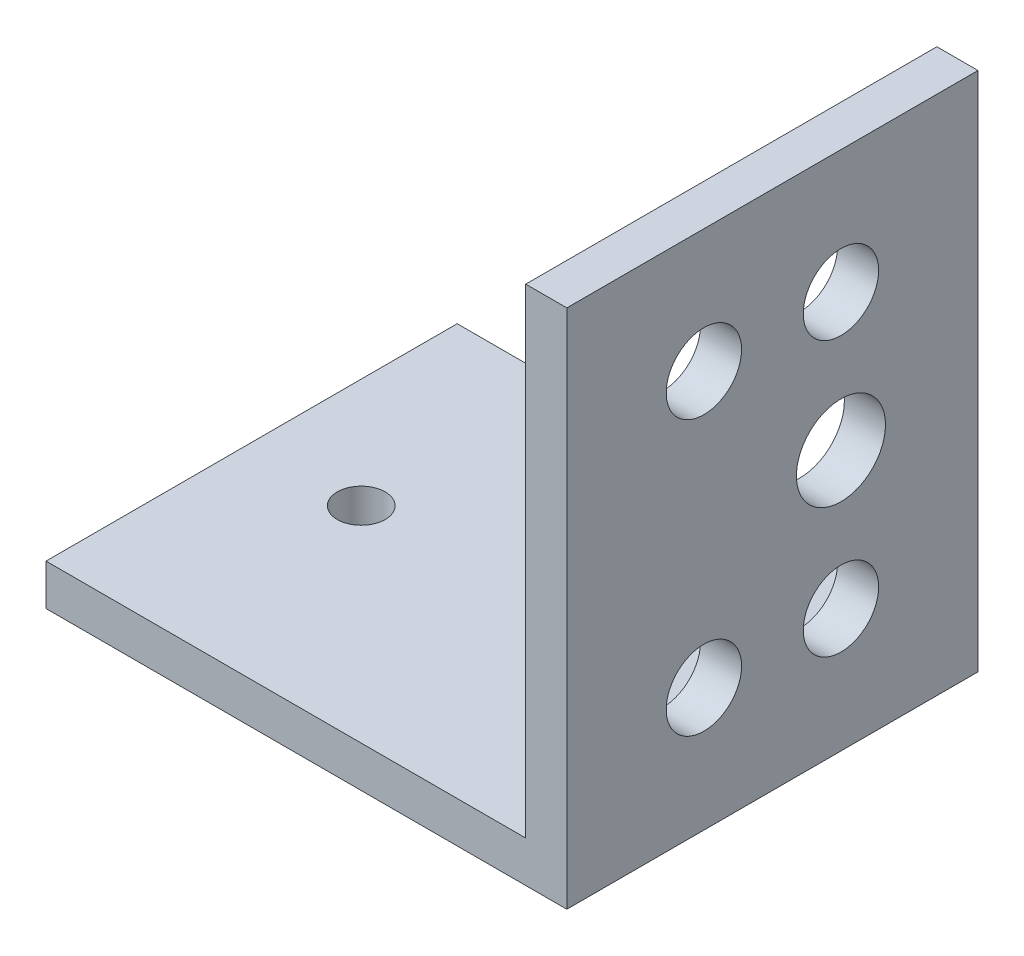
SolidWorks part; units mm, degrees
ref_plane "前视基准面" through (0, 0, 0) normal (0, 0, 1) x (1, 0, 0)
ref_plane "上视基准面" through (0, 0, 0) normal (0, 1, 0) x (1, 0, 0)
ref_plane "右视基准面" through (0, 0, 0) normal (1, 0, 0) x (0, 0, -1)
sketch "草图1" plane through (0, 0, 0) normal (0, 0, 1) x (1, 0, 0)
  line L0 (0, 0) -> (0, 38)
  line L1 (0, 0) -> (-38, 0)
  line L2 (-38, 0) -> (-38, 3)
  line L3 (-38, 3) -> (-3, 3)
  line L4 (-3, 3) -> (-3, 38)
  line L5 (-3, 38) -> (0, 38)
  dimension "D1" = 35
  dimension "D2" = 3
  dimension "D3" = 3
  dimension "D4" = 35
extrude "凸台-拉伸1" add sketch "草图1" along normal blind 30
sketch "草图3" plane through (0, 3, 0) normal (0, 1, 0) x (1, 0, 0)
  line L0 (-38, -15) -> (-9.0306, -15) construction
  line L1 (-38, -30) -> (-38, 0) construction
  line L2 (-30, -15) -> (-10.0395, -16.2558) construction
  circle A0 centre (-30, -15) radius 1.75
  circle A1 centre (-10.0395, -16.2558) radius 1.75
  dimension "D2" = 3.5
  dimension "D3" = 3.5
  dimension "D1" = 3.6
  dimension "D4" = 20
  dimension "D5" = 8
extrude "切除-拉伸2" cut sketch "草图3" against normal blind 10
sketch "草图4" plane through (0, 0, 0) normal (1, 0, 0) x (0, 0, -1)
  line L0 (0, 0) -> (0, 38) construction
  line L2 (-30, 38) -> (0, 38) construction
  circle A0 centre (-10, 29) radius 2.75
  circle A1 centre (-10, 19) radius 3.25
  circle A2 centre (-10, 9) radius 2.75
  circle A3 centre (-20, 29) radius 2.75
  circle A4 centre (-20, 9) radius 2.75
  dimension "D3" = 5.5
  dimension "D4" = 6.5
  dimension "D5" = 5.5
  dimension "D7" = 5.5
  dimension "D9" = 5.5
  dimension "D1" = 10
  dimension "D2" = 10
  dimension "D6" = 10
  dimension "D8" = 20
  dimension "D10" = 10
  dimension "D11" = 19
extrude "切除-拉伸3" cut sketch "草图4" against normal up to next
